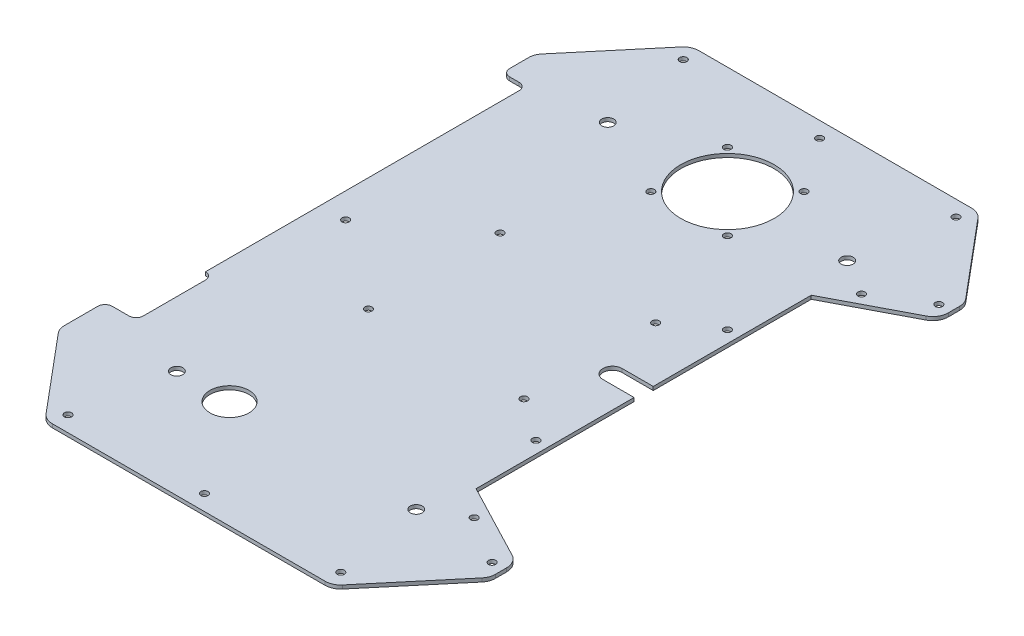
SolidWorks part; units mm, degrees
ref_plane "Plan de face" through (0, 0, 0) normal (0, 0, 1) x (1, 0, 0)
ref_plane "Plan de dessus" through (0, 0, 0) normal (0, 1, 0) x (1, 0, 0)
ref_plane "Plan de droite" through (0, 0, 0) normal (1, 0, 0) x (0, 0, -1)
sketch "Esquisse1" plane through (0, 0, 0) normal (0, 1, 0) x (1, 0, 0)
  line L0 (-90, 135) -> (90, 135)
  line L1 (-90, 135) -> (90, 135) construction
  line L2 (-90, 135) -> (-90, 0) construction
  line L4 (90, 135) -> (90, 88.3098) construction
  line L8 (90, 135) -> (90, 88.3098)
  line L9 (90, 88.3098) -> (55, 70)
  line L10 (55, 70) -> (55, 0)
  line L16 (-90, 0) -> (-90, 135)
  line L18 (55, 0) -> (-90, 0)
  point P0 (0, 0)
  dimension "D1" = 180
  dimension "D2" = 135
  dimension "D3" = 39.5
  dimension "D4" = 70
  dimension "D5" = 35
  dimension "D6" = 90
extrude "Boss.-Extru.1" add sketch "Esquisse1" along normal blind 1.5
chamfer "Chanfrein1" distance 30 angle 50 2 edges at (90, 0.75, -135) (-90, 0.75, -135) first distance on face at (0, 0.75, -135)
sketch "Esquisse2" plane through (0, 1.5, 0) normal (0, 1, 0) x (1, 0, 0)
  line L0 (-90, 0) -> (55, 0) construction
  line L1 (-50, 0) -> (50, 0) construction
  line L2 (-50, 0) -> (-50, 90) construction
  line L3 (-50, 90) -> (50, 90) construction
  line L4 (50, 0) -> (50, 90) construction
  line L5 (60, 135) -> (-60, 135) construction
  line L6 (55, 0) -> (55, 70) construction
  circle A0 centre (-50, 90) radius 2.5
  circle A1 centre (50, 90) radius 2.5
  circle A2 centre (50, 40) radius 1.5
  dimension "D3" = 5
  dimension "D4" = 3
  dimension "D1" = 45
  dimension "D2" = 100
  dimension "D5" = 5
  dimension "D6" = 40
extrude "Enlèv. mat.-Extru.1" cut sketch "Esquisse2" against normal up to next
sketch "Esquisse5" plane through (0, 1.5, 0) normal (0, 1, 0) x (1, 0, 0)
  line L0 (90, 88.3098) -> (90, 99.2474) construction
  line L1 (55, 70) -> (90, 88.3098) construction
  line L2 (65.0874, 80.9199) -> (67.4051, 76.4896) construction
  line L4 (-60, 135) -> (-90, 99.2474) construction
  line L5 (-56.969, 128.5) -> (-56.969, 135) construction
  line L6 (60, 135) -> (-60, 135) construction
  line L7 (0, 128.5) -> (0, 135) construction
  line L8 (56.969, 128.5) -> (56.969, 135) construction
  line L10 (90, 99.2474) -> (60, 135) construction
  line L11 (-56.969, 128.5) -> (-61.9483, 132.6781) construction
  line L13 (56.969, 128.5) -> (61.9483, 132.6781) construction
  line L15 (85, 93.3098) -> (90, 93.3098) construction
  circle A0 centre (85, 93.3098) radius 1.5
  circle A1 centre (65.0874, 80.9199) radius 1.5
  circle A3 centre (-56.969, 128.5) radius 1.5
  circle A4 centre (0, 128.5) radius 1.5
  circle A5 centre (56.969, 128.5) radius 1.5
  dimension "D3" = 3
  dimension "D6" = 3
  dimension "D2" = 5
  dimension "D4" = 5
  dimension "D5" = 14
  dimension "D10" = 6.5
extrude "Enlèv. mat.-Extru.4" cut sketch "Esquisse5" against normal through all
fillet "Congé2" radius 6.5 5 edges at (90, 0.75, -99.2474) (60, 0.75, -135) (-60, 0.75, -135) (-90, 0.75, -99.2474) (90, 0.75, -88.3098)
mirror "Symétrie1" about plane through (55, 1.5, 0) normal (0, 0, -1) of bodies 106 102
sketch "Esquisse3" plane through (0, 1.5, 0) normal (0, 1, 0) x (1, 0, 0)
  line L0 (32.5, 27.5) -> (0, 0) construction
  line L1 (0, 0) -> (32.5, -27.5) construction
  line L2 (0, -0.825) -> (0, 0.825) construction
  line L6 (42, 0) -> (55, 0) construction
  line L7 (42, 4) -> (55, 4)
  line L8 (42, -4) -> (55, -4)
  line L9 (55, -70) -> (55, 70) construction
  circle A1 centre (32.5, -27.5) radius 1.5
  circle A2 centre (32.5, 27.5) radius 1.5
  arc A7 (42, 4) -> (42, -4) centre (42, 0) ccw
  arc A8 (55, -4) -> (55, 4) centre (55, 0) ccw
  circle A9 centre (-32.5, -27.5) radius 1.5
  circle A10 centre (-32.5, 27.5) radius 1.5
  point P17 (48.5, 0)
  dimension "D2" = 3
  dimension "D10" = 4
  dimension "D3" = 55
  dimension "D4" = 32.5
  dimension "D9" = 42
extrude "Enlèv. mat.-Extru.2" cut sketch "Esquisse3" against normal through all
sketch "Esquisse4" plane through (0, 1.5, 0) normal (0, 1, 0) x (1, 0, 0)
  line L0 (-36.15, -90) -> (-19.85, -90) construction
  line L2 (-50, -90) -> (-28, -90) construction
  line L3 (16, 106) -> (-16, 106) construction
  line L4 (16, 106) -> (16, 74) construction
  line L5 (16, 74) -> (-16, 74) construction
  line L6 (-16, 106) -> (-16, 74) construction
  line L7 (16, 106) -> (-16, 74) construction
  line L8 (16, 74) -> (-16, 106) construction
  line L11 (-50, 90) -> (0, 90) construction
  line L12 (0, 90) -> (0, 0) construction
  circle A0 centre (-28, -90) radius 8.15
  circle A1 centre (0, 90) radius 19.5
  circle A2 centre (16, 106) radius 1.5
  circle A4 centre (-16, 106) radius 1.5
  circle A5 centre (-16, 74) radius 1.5
  circle A6 centre (16, 74) radius 1.5
  point P5 (-28, -90)
  dimension "D1" = 22
  dimension "D3" = 16.3
  dimension "D5" = 3
  dimension "D2" = 39
  dimension "D4" = 32
extrude "Enlèv. mat.-Extru.3" cut sketch "Esquisse4" against normal through all and the other way through all
sketch "Esquisse6" plane through (0, 1.5, 0) normal (0, 1, 0) x (1, 0, 0)
  line L0 (-90, 96.8816) -> (-90, -96.8816) construction
  line L1 (-90, -80) -> (-80, -80)
  line L2 (-90, -80) -> (-90, 86)
  line L3 (-90, 86) -> (-80, 86)
  line L4 (-80, -80) -> (-80, 86)
  line L6 (-80, -80) -> (-77, -80)
  line L7 (-80, -80) -> (-80, -48)
  line L8 (-80, -48) -> (-77, -48)
  line L9 (-77, -80) -> (-77, -48)
  circle A0 centre (-50, -90) radius 2.5 construction
  circle A2 centre (-69.5, 0) radius 1.5
  circle A3 centre (-50, 90) radius 2.5 construction
  dimension "D9" = 3
  dimension "D3" = 4
  dimension "D1" = 10
  dimension "D2" = 10
  dimension "D4" = 3
  dimension "D5" = 32
  dimension "D6" = 20.5
extrude "Enlèv. mat.-Extru.5" cut sketch "Esquisse6" against normal up to next contours L1 L4 L3 | L6 L9 L8 L4 | A2 region at (-85, 1.5, -3) region at (-78.5, 1.5, 64) region at (-69.5, 1.5, 0)
fillet "Congé1" radius 3 5 edges at (-77, 0.75, 80) (-77, 0.75, 48) (-80, 0.75, -86) (-90, 0.75, 80) (-90, 0.75, -86)
